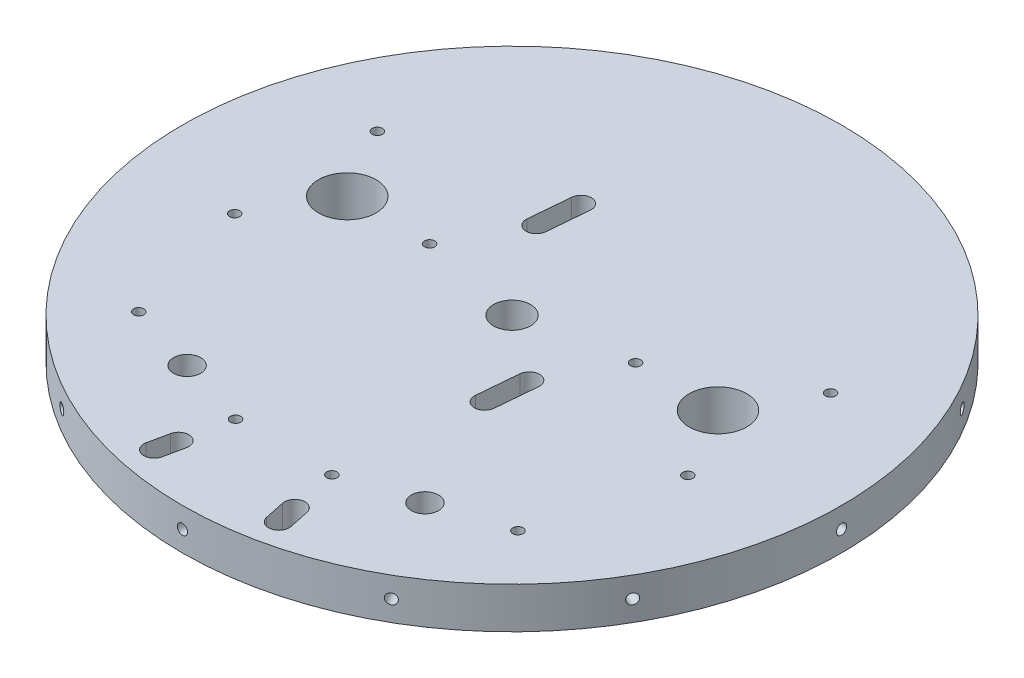
SolidWorks part; units mm, degrees
material "6061 Alloy"
ref_plane "Front Plane" through (0, 0, 0) normal (0, 0, 1) x (1, 0, 0)
ref_plane "Top Plane" through (0, 0, 0) normal (0, 1, 0) x (1, 0, 0)
ref_plane "Right Plane" through (0, 0, 0) normal (1, 0, 0) x (0, 0, -1)
sketch "Sketch1" plane through (0, 0, 0) normal (0, 1, 0) x (1, 0, 0)
  circle A0 centre (0, 0) radius 80
extrude "Boss-Extrude1" add sketch "Sketch1" against normal blind 10
sketch "Sketch3" plane through (0, 0, 0) normal (0, 1, 0) x (1, 0, 0)
  circle A0 centre (0, 0) radius 4.5
extrude "Cut-Extrude1" cut sketch "Sketch3" against normal blind 12
sketch "Sketch4" plane through (0, 0, 0) normal (0, 1, 0) x (1, 0, 0)
  line L1 (45, 5) -> (-45, 5)
  circle A2 centre (-45, 5) radius 7
  circle A3 centre (45, 5) radius 7
  point P5 (0, 0)
extrude "Cut-Extrude2" cut sketch "Sketch4" against normal blind 12 contours A2 | A3 region at (-51.802, 0, -5) region at (45, 0, -11.802)
ref_plane "Plane1" through (0, 0, 80) normal (0, 0, 1) x (1, 0, 0)
sketch "Sketch5" plane through (0, 0, 80) normal (0, 0, 1) x (1, 0, 0)
  line L0 (80, 0) -> (-80, 0) construction
  circle A0 centre (0, -5) radius 1.25
  dimension "D1" = 5
extrude "Cut-Extrude3" cut sketch "Sketch5" against normal blind 15
pattern_circular "CirPattern1" count 12 over 360 about axis through (0, 0, 0) along (0, 1, 0) of "Cut-Extrude3"
sketch "Sketch6" plane through (0, 0, 0) normal (0, 1, 0) x (1, 0, 0)
  line L2 (-45, 5) -> (-25, 5) construction
  line L3 (45, 5) -> (25, 5) construction
  circle A2 centre (-25, 5) radius 1.25
  circle A3 centre (25, 5) radius 1.25
  circle A4 centre (-55, 22.3205) radius 1.25
  circle A5 centre (-55, -12.3205) radius 1.25
  circle A6 centre (55, 22.3205) radius 1.25
  circle A7 centre (55, -12.3205) radius 1.25
  point P7 (-45, 5)
  point P18 (45, 5)
  dimension "D1" = 3
  dimension "D2" = 3
extrude "Cut-Extrude4" cut sketch "Sketch6" against normal up to next contours A2 | A3 | A4 | A5 | A7 | A6 region at (-25, 0, -5) region at (25, 0, -5) region at (-55, 0, -22.3205) region at (-55, 0, 12.3205) region at (55, 0, -22.3205) region at (55, 0, 12.3205)
sketch "Sketch9" plane through (0, -10, 0) normal (0, -1, 0) x (1, 0, 0)
  circle A0 centre (0, 0) radius 12.5
extrude "Cut-Extrude5" cut sketch "Sketch9" against normal blind 3
sketch "Sketch10" plane through (0, 0, 0) normal (0, 1, 0) x (1, 0, 0)
  line L0 (0, 0) -> (0, -80) construction
  line L1 (0, 0) -> (28.8675, -50)
  line L2 (0, 0) -> (-28.8675, -50)
  line L4 (-28.8675, -50) -> (28.8675, -50)
  circle A0 centre (0, 0) radius 80 construction
  circle A4 centre (-28.8675, -50) radius 3.3
  circle A5 centre (28.8675, -50) radius 3.3
  point P12 (17.3205, -60)
  dimension "D1" = 30
  dimension "D2" = 30
extrude "Cut-Extrude6" cut sketch "Sketch10" against normal up to next contours L1 A5 L4 | L4 A5 L1 | A4 region at (29.2314, 0, 50.2101) region at (27.0481, 0, 48.9496)
sketch "Sketch11" plane through (0, 0, 0) normal (0, 1, 0) x (1, 0, 0)
  line L0 (0, 0) -> (0, -80) construction
  line L1 (28.8675, -50) -> (0, -59.1019) construction
  line L2 (0, -59.1019) -> (-28.8675, -50) construction
  circle A0 centre (0, 0) radius 80 construction
  circle A1 centre (11.7006, -55.4127) radius 1.25
  circle A2 centre (-11.7006, -55.4127) radius 1.25
  circle A3 centre (46.0344, -44.5873) radius 1.25
  circle A4 centre (-46.0344, -44.5873) radius 1.25
  point P20 (28.8675, -50)
  point P22 (-28.8675, -50)
  dimension "D2" = 18
  dimension "D3" = 18
  dimension "D1" = 145
  dimension "D4" = 2
  dimension "D5" = 2
extrude "Cut-Extrude7" cut sketch "Sketch11" against normal up to next
sketch "Sketch12" plane through (0, 0, 0) normal (0, 1, 0) x (1, 0, 0)
  line L0 (0, 0) -> (16.5279, -78.2741) construction
  line L1 (0, 0) -> (-16.5279, -78.2741) construction
  line L4 (16.5603, -66.3269) -> (17.5933, -71.219)
  line L5 (12.7012, -72.252) -> (11.6682, -67.3599)
  line L6 (-11.6682, -67.3599) -> (-12.7012, -72.252)
  line L7 (-16.5603, -66.3269) -> (-17.5933, -71.219)
  arc A1 (16.5603, -66.3269) -> (11.6682, -67.3599) centre (14.1142, -66.8434) ccw
  arc A2 (-11.6682, -67.3599) -> (-16.5603, -66.3269) centre (-14.1142, -66.8434) ccw
  arc A3 (-17.5933, -71.219) -> (-12.7012, -72.252) centre (-15.1472, -71.7355) ccw
  arc A4 (12.7012, -72.252) -> (17.5933, -71.219) centre (15.1472, -71.7355) ccw
  circle A5 centre (0, 0) radius 80 construction
  dimension "D1" = 5
  dimension "D2" = 5
extrude "Cut-Extrude8" cut sketch "Sketch12" against normal up to next
sketch "Sketch13" plane through (0, 0, 0) normal (0, 1, 0) x (1, 0, 0)
  line L0 (28.8675, -50) -> (0, 0) construction
  line L1 (0, 0) -> (-40, 69.282) construction
  line L2 (33.1976, -47.5) -> (4.3301, 2.5) construction
  line L3 (18.0385, -14.28) -> (17.6027, -19.2609)
  line L4 (13.0575, -13.8442) -> (12.6218, -18.8252)
  line L5 (-17.8099, 0.4442) -> (-13.1901, 53.2494) construction
  line L6 (9.2515, -86.0316) -> (21.4088, 52.9265) construction
  line L7 (-12.7916, 29.1194) -> (-13.2274, 24.1384)
  line L8 (-17.7726, 29.5552) -> (-18.2084, 24.5742)
  line L9 (-12.5737, 31.6099) -> (-13.4453, 21.6479)
  line L10 (-17.5547, 32.0457) -> (-18.4263, 22.0837)
  line L11 (18.2564, -11.7895) -> (17.3848, -21.7514)
  line L12 (13.2754, -11.3537) -> (12.4039, -21.3156)
  circle A0 centre (0, 0) radius 80 construction
  arc A11 (-12.5737, 31.6099) -> (-17.5547, 32.0457) centre (-15.0642, 31.8278) ccw
  arc A12 (-18.4263, 22.0837) -> (-13.4453, 21.6479) centre (-15.9358, 21.8658) ccw
  arc A14 (18.2564, -11.7895) -> (13.2754, -11.3537) centre (15.7659, -11.5716) ccw
  arc A15 (-13.4521, 23.2998) -> (-13.2274, 24.1384) centre (-15.7179, 24.3563) ccw
  arc A16 (12.4039, -21.3156) -> (17.3848, -21.7514) centre (14.8943, -21.5335) ccw
  point P16 (-15.5, 26.8468)
  point P19 (15.3301, -16.5526)
  point P22 (-15.5, 26.8468)
  point P25 (15.3301, -16.5526)
  point P26 (15.3301, -16.5526)
  dimension "D2" = 35
  dimension "D3" = 35
  dimension "D1" = 5
extrude "Cut-Extrude10" cut sketch "Sketch13" against normal up to next contours L10 A12 L9 L7 A11 L8 | L12 A16 L11 L3 A14 L4 region at (15.3301, 0, 16.5526) region at (-15.5, 0, -26.8468)
